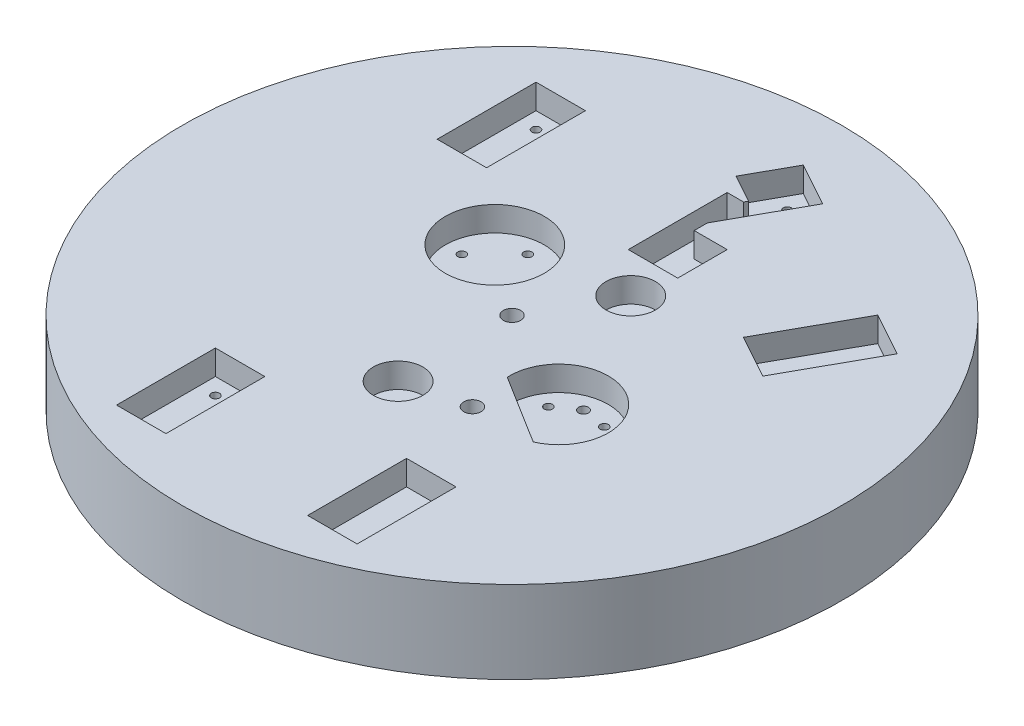
SolidWorks part; units mm, degrees
material "1.0045 (S355JR)"
ref_plane "Front Plane" through (0, 0, 0) normal (0, 0, 1) x (1, 0, 0)
ref_plane "Top Plane" through (0, 0, 0) normal (0, 1, 0) x (1, 0, 0)
ref_plane "Right Plane" through (0, 0, 0) normal (1, 0, 0) x (0, 0, -1)
sketch "Sketch1" plane through (0, 0, 0) normal (0, 1, 0) x (1, 0, 0)
  circle A0 centre (0, 0) radius 200
  dimension "D1" = 400
extrude "Boss-Extrude1" add sketch "Sketch1" along normal blind 50
sketch "Sketch2" plane through (0, 50, 0) normal (0, 1, 0) x (1, 0, 0)
  line L0 (-42.3277, 31.8965) -> (60.9712, -32.5462) construction
  line L1 (31.0011, -33.8863) -> (72.9452, -60.0529)
  circle A1 centre (0, -69.1139) radius 15
  arc A2 (72.9452, -60.0529) -> (31.0011, -33.8863) centre (60.9712, -32.5462) ccw
  circle A3 centre (25.6946, 46.3547) radius 15
  circle A4 centre (-42.3277, 31.8965) radius 30
  point P15 (0, 0)
  point P39 (250, 0)
  dimension "D3" = 30
  dimension "D6" = 60
  dimension "D10" = 30
  dimension "D11" = 69.1139
  dimension "D13" = 60
  dimension "D2" = 42.3277
  dimension "D4" = 31.8965
  dimension "D5" = 25.6946
  dimension "D7" = 46.3547
  dimension "D8" = 32.5462
  dimension "D9" = 60.9712
  dimension "D12" = 17
extrude "Cut-Extrude1" cut sketch "Sketch2" against normal blind 15
sketch "Sketch3" plane through (0, 50, 0) normal (0, 1, 0) x (1, 0, 0)
  line L57 (43.1123, -107.1139) -> (73.1123, -107.1139)
  line L92 (110.8144, 111.2209) -> (119.5606, 106.3728)
  line L93 (110.8144, 111.2209) -> (81.726, 58.7436)
  line L94 (81.726, 58.7436) -> (107.9646, 44.1994)
  line L95 (107.9646, 44.1994) -> (137.053, 96.6767)
  line L96 (137.053, 96.6767) -> (110.8144, 111.2209)
  line L97 (-85.3277, 129.8965) -> (-115.3277, 129.8965)
  line L98 (-115.3277, 129.8965) -> (-115.3277, 69.8965)
  line L99 (-115.3277, 69.8965) -> (-85.3277, 69.8965)
  line L100 (-85.3277, 129.8965) -> (-85.3277, 69.8965)
  line L104 (73.1123, -107.1139) -> (73.1123, -167.1139)
  line L107 (73.1123, -167.1139) -> (43.1123, -167.1139)
  line L108 (-42.8877, -107.1139) -> (-72.8877, -107.1139)
  line L109 (-72.8877, -107.1139) -> (-72.8877, -167.1139)
  line L110 (-72.8877, -167.1139) -> (-42.8877, -167.1139)
  line L111 (-42.8877, -107.1139) -> (-42.8877, -167.1139)
  line L112 (43.1123, -107.1139) -> (43.1123, -167.1139)
  line L113 (9.3583, 167.4584) -> (35.597, 152.9142)
  line L114 (0.6723, 129.8965) -> (10.6723, 129.8965)
  line L116 (0.6723, 69.8965) -> (30.6723, 69.8965)
  line L117 (30.6723, 99.8965) -> (30.6723, 69.8965)
  line L118 (35.597, 152.9142) -> (10.6723, 107.9486)
  line L120 (-5.1859, 141.2198) -> (9.3583, 167.4584)
  line L121 (30.6723, 99.8965) -> (10.6723, 99.8965)
  line L122 (10.6723, 99.8965) -> (10.6723, 107.9486)
  line L123 (10.6723, 129.8965) -> (11.7464, 131.8342)
  line L124 (-5.1859, 141.2198) -> (11.7464, 131.8342)
  line L125 (0.6723, 129.8965) -> (0.6723, 69.8965)
  line L126 (81.726, 58.7436) -> (10.6723, 98.129) construction
  line L127 (10.6723, 129.8965) -> (10.6723, 98.129) construction
  point P0 (0, 0)
  point P57 (0, 0)
  dimension "D2" = 81.726
  dimension "D3" = 10
  dimension "D4" = 58.7436
  dimension "D5" = 30
  dimension "D6" = 107.9646
  dimension "D7" = 111.2209
  dimension "D8" = 30
  dimension "D9" = 69.8965
  dimension "D10" = 60
  dimension "D11" = 30
  dimension "D12" = 30
  dimension "D13" = 30
  dimension "D14" = 30
  dimension "D16" = 86
  dimension "D17" = 20
  dimension "D18" = 30
  dimension "D19" = 60
  dimension "D15" = 30.6723
  dimension "D20" = 30
  dimension "D21" = 60
  dimension "D22" = 43.1123
  dimension "D23" = 107.1139
  dimension "D24" = 107.1139
  dimension "D25" = 42.8877
  dimension "D26" = 2.2155
  dimension "D27" = 85.3277
hole_wizard "M12x1.5 Tapped Hole1" positions "Sketch14" profile "Sketch15" tap size "M12x1.5" standard "ISO"
sketch "Sketch14" plane through (0, 35, 0) normal (0, 1, 0) x (1, 0, 0)
  point P0 (25.6946, 46.3547)
  point P3 (0, -69.1139)
sketch "Sketch15" plane through (25.6946, 35, -46.3547) normal (1, 0, 0) x (0, 0, 1)
  line L0 (0, 0) -> (0, 28.5)
  line L1 (0, 28.5) -> (5.25, 25.3455)
  line L2 (5.25, 25.3455) -> (5.25, 0)
  line L5 (5.25, 0) -> (0, 0)
  line L10 (0, 28.5) -> (-5.25, 25.3455) construction
  line L11 (0, -6.35) -> (0, 107.95) construction
  dimension "Tap Drill Dia." = 10.5
  dimension "Tap Drill Depth" = 28.5
  dimension "Drill Angle" = 118
cosmetic thread "Hole Thread41" parameters "D1"=24, "D2"=12
cosmetic thread "Hole Thread42" parameters "D1"=24, "D2"=12
sketch "Sketch16" plane through (0, 35, 0) normal (0, 1, 0) x (1, 0, 0)
  line L0 (-42.3277, 31.8965) -> (60.9712, -32.5462) construction
  circle A0 centre (44.0024, -21.9603) radius 3
  point P4 (-42.3277, 31.8965)
  point P6 (60.9712, -32.5462)
  dimension "D1" = 6
  dimension "D2" = 20
hole_wizard "M6 Tapped Hole1" positions "Sketch17" profile "Sketch18" tap size "M6" standard "ISO"
sketch "Sketch17" plane through (0, 35, 0) normal (0, 1, 0) x (1, 0, 0)
  point P0 (44.0024, -21.9603)
sketch "Sketch18" plane through (44.0024, 35, 21.9603) normal (1, 0, 0) x (0, 0, 1)
  line L0 (0, 0) -> (0, 15)
  line L1 (0, 15) -> (2.5, 13.4978)
  line L2 (2.5, 13.4978) -> (2.5, 0)
  line L5 (2.5, 0) -> (0, 0)
  line L10 (0, 15) -> (-2.5, 13.4978) construction
  line L11 (0, -6.35) -> (0, 107.95) construction
  dimension "Tap Drill Dia." = 5
  dimension "Tap Drill Depth" = 15
  dimension "Drill Angle" = 118
cosmetic thread "Hole Thread49" parameters "D1"=12, "D2"=6
pattern_circular "CirPattern5" count 3 over 180 about axis through (60.9712, 35, 32.5462) along (0, 1, 0) of "M6 Tapped Hole1" reverse direction yes
cosmetic thread "Hole Thread50" parameters "D1"=12, "D2"=6
cosmetic thread "Hole Thread51" parameters "D1"=12, "D2"=6
cosmetic thread "Hole Thread52" parameters "D1"=12, "D2"=6
cosmetic thread "Hole Thread81" parameters "D1"=12, "D2"=6
sketch "Sketch19" plane through (0, 35, 0) normal (0, 1, 0) x (1, 0, 0)
  circle A0 centre (-42.3277, 51.8965) radius 2
  point P2 (-42.3277, 31.8965)
  dimension "D1" = 4
  dimension "D2" = 20
hole_wizard "M6 Tapped Hole2" positions "Sketch20" profile "Sketch21" tap size "M6" standard "ISO"
sketch "Sketch20" plane through (0, 35, 0) normal (0, 1, 0) x (1, 0, 0)
  point P0 (-42.3277, 51.8965)
sketch "Sketch21" plane through (-42.3277, 35, -51.8965) normal (1, 0, 0) x (0, 0, 1)
  line L0 (0, 0) -> (0, 15)
  line L1 (0, 15) -> (2.5, 13.4978)
  line L2 (2.5, 13.4978) -> (2.5, 0)
  line L5 (2.5, 0) -> (0, 0)
  line L10 (0, 15) -> (-2.5, 13.4978) construction
  line L11 (0, -6.35) -> (0, 107.95) construction
  dimension "Tap Drill Dia." = 5
  dimension "Tap Drill Depth" = 15
  dimension "Drill Angle" = 118
cosmetic thread "Hole Thread53" parameters "D1"=12, "D2"=6
pattern_circular "CirPattern6" count 4 over 360 about axis through (-42.3277, 35, -31.8965) along (0, 1, 0) of "M6 Tapped Hole2"
cosmetic thread "Hole Thread54" parameters "D1"=12, "D2"=6
cosmetic thread "Hole Thread55" parameters "D1"=12, "D2"=6
cosmetic thread "Hole Thread56" parameters "D1"=12, "D2"=6
sketch "Sketch22" plane through (0, 50, 0) normal (0, 1, 0) x (1, 0, 0)
  line L2 (35.989, -60.0062) -> (-0.0148, 0.0248) construction
  circle A1 centre (-0.0148, 0.0248) radius 4
  circle A2 centre (35.989, -60.0062) radius 6
  dimension "D4" = 8
  dimension "D1" = 12
  dimension "D3" = 70
hole_wizard "M12x1.5 Tapped Hole2" positions "Sketch25" profile "Sketch26" tap size "M12x1.5" standard "ISO"
sketch "Sketch25" plane through (0, 50, 0) normal (0, 1, 0) x (1, 0, 0)
  point P0 (-0.0148, 0.0248)
sketch "Sketch26" plane through (-0.0148, 50, -0.0248) normal (1, 0, 0) x (0, 0, 1)
  line L0 (0, 0) -> (0, 28.5)
  line L1 (0, 28.5) -> (5.25, 25.3455)
  line L2 (5.25, 25.3455) -> (5.25, 0)
  line L5 (5.25, 0) -> (0, 0)
  line L10 (0, 28.5) -> (-5.25, 25.3455) construction
  line L11 (0, -6.35) -> (0, 107.95) construction
  dimension "Tap Drill Dia." = 10.5
  dimension "Tap Drill Depth" = 28.5
  dimension "Drill Angle" = 118
cosmetic thread "Hole Thread86" parameters "D1"=24, "D2"=12
extrude "Cut-Extrude2" cut sketch "Sketch3" against normal blind 15 contours L100 L97 L98 L99 | L95 L96 L92 L93 L94 | L111 L108 L109 L110 | L112 L107 L104 L57 | L117 L116 L125 L114 L123 L124 L120 L113 L118 L122 L121 region at (109.3895, 50, -77.7101) region at (-100.3277, 50, -99.8965) region at (-57.8877, 50, 137.1139)
sketch "Sketch27" plane through (0, 35, 0) normal (0, 1, 0) x (1, 0, 0)
  line L0 (137.053, 96.6767) -> (110.8144, 111.2209) construction
  line L1 (107.9646, 44.1994) -> (137.053, 96.6767) construction
  line L2 (30.6723, 99.8965) -> (30.6723, 69.8965) construction
  line L3 (81.726, 58.7436) -> (107.9646, 44.1994) construction
  line L4 (-115.3277, 129.8965) -> (-115.3277, 69.8965) construction
  line L5 (-85.3277, 129.8965) -> (-115.3277, 129.8965) construction
  line L6 (-115.3277, 69.8965) -> (-85.3277, 69.8965) construction
  line L7 (-42.8877, -107.1139) -> (-72.8877, -107.1139) construction
  line L8 (-72.8877, -107.1139) -> (-72.8877, -167.1139) construction
  line L9 (-72.8877, -167.1139) -> (-42.8877, -167.1139) construction
  line L10 (0.6723, 69.8965) -> (30.6723, 69.8965) construction
  line L11 (-72.8877, -107.1139) -> (-72.8877, -167.1139) construction
  line L12 (73.1123, -107.1139) -> (73.1123, -167.1139) construction
  line L13 (43.1123, -107.1139) -> (73.1123, -107.1139) construction
  line L14 (73.1123, -167.1139) -> (43.1123, -167.1139) construction
  line L15 (9.3583, 167.4584) -> (35.597, 152.9142) construction
  line L16 (-5.1859, 141.2198) -> (9.3583, 167.4584) construction
  circle A0 centre (123.4587, 92.7785) radius 3
  circle A1 centre (104.0665, 57.7937) radius 3
  circle A2 centre (-105.3277, 119.8965) radius 3
  circle A3 centre (-105.3277, 79.8965) radius 3
  circle A4 centre (-62.8877, -117.1139) radius 3
  circle A5 centre (-62.8877, -157.1139) radius 3
  circle A6 centre (63.1123, -117.1139) radius 3
  circle A7 centre (63.1123, -157.1139) radius 3
  circle A8 centre (20.6723, 79.8965) radius 3
  circle A9 centre (13.2565, 153.8642) radius 3
  dimension "D1" = 6
  dimension "D2" = 6
  dimension "D9" = 6
  dimension "D10" = 6
  dimension "D14" = 10
  dimension "D15" = 6
  dimension "D18" = 6
  dimension "D20" = 10
  dimension "D22" = 10
  dimension "D23" = 6
  dimension "D24" = 6
  dimension "D25" = 6
  dimension "D30" = 6
  dimension "D3" = 10
  dimension "D4" = 10
  dimension "D5" = 10
  dimension "D6" = 10
  dimension "D7" = 10
  dimension "D8" = 10
  dimension "D11" = 10
  dimension "D12" = 10
  dimension "D13" = 10
  dimension "D16" = 10
  dimension "D17" = 10
  dimension "D19" = 10
  dimension "D21" = 10
  dimension "D26" = 10
  dimension "D27" = 10
  dimension "D28" = 10
  dimension "D29" = 10
hole_wizard "M6 Tapped Hole3" positions "Sketch30" profile "Sketch31" tap size "M6" standard "ISO"
sketch "Sketch30" plane through (0, 35, 0) normal (0, 1, 0) x (1, 0, 0)
  point P0 (123.4587, 92.7785)
  point P3 (104.0665, 57.7937)
  point P6 (-105.3277, 119.8965)
  point P9 (-105.3277, 79.8965)
  point P12 (-62.8877, -117.1139)
  point P15 (-62.8877, -157.1139)
  point P18 (63.1123, -117.1139)
  point P21 (63.1123, -157.1139)
  point P24 (13.2565, 153.8642)
  point P27 (20.6723, 79.8965)
sketch "Sketch31" plane through (123.4587, 35, -92.7785) normal (1, 0, 0) x (0, 0, 1)
  line L0 (0, 0) -> (0, 15)
  line L1 (0, 15) -> (2.5, 13.4978)
  line L2 (2.5, 13.4978) -> (2.5, 0)
  line L5 (2.5, 0) -> (0, 0)
  line L10 (0, 15) -> (-2.5, 13.4978) construction
  line L11 (0, -6.35) -> (0, 107.95) construction
  dimension "Tap Drill Dia." = 5
  dimension "Tap Drill Depth" = 15
  dimension "Drill Angle" = 118
cosmetic thread "Hole Thread87" parameters "D1"=12, "D2"=6
cosmetic thread "Hole Thread88" parameters "D1"=12, "D2"=6
cosmetic thread "Hole Thread89" parameters "D1"=12, "D2"=6
cosmetic thread "Hole Thread90" parameters "D1"=12, "D2"=6
cosmetic thread "Hole Thread91" parameters "D1"=12, "D2"=6
cosmetic thread "Hole Thread92" parameters "D1"=12, "D2"=6
cosmetic thread "Hole Thread93" parameters "D1"=12, "D2"=6
cosmetic thread "Hole Thread94" parameters "D1"=12, "D2"=6
cosmetic thread "Hole Thread95" parameters "D1"=12, "D2"=6
cosmetic thread "Hole Thread96" parameters "D1"=12, "D2"=6
sketch "Sketch32" plane through (0, 35, 0) normal (0, 1, 0) x (1, 0, 0)
  line L0 (60.9712, -32.5462) -> (44.0024, -21.9603) construction
  line L1 (56.4578, -13.0621) -> (60.9712, -32.5462) construction
  circle A0 centre (56.4578, -13.0621) radius 3
  arc A1 (72.9452, -60.0529) -> (31.0011, -33.8863) centre (60.9712, -32.5462) ccw construction
  dimension "D1" = 6
  dimension "D2" = 20
  dimension "D3" = 45
extrude "Cut-Extrude3" cut sketch "Sketch32" against normal blind 15
hole_wizard "M12x1.5 Tapped Hole3" positions "Sketch33" profile "Sketch34" tap size "M12x1.5" standard "ISO"
sketch "Sketch33" plane through (0, 50, 0) normal (0, 1, 0) x (1, 0, 0)
  point P0 (35.989, -60.0062)
sketch "Sketch34" plane through (35.989, 50, 60.0062) normal (1, 0, 0) x (0, 0, 1)
  line L0 (0, 0) -> (0, 28.5)
  line L1 (0, 28.5) -> (5.25, 25.3455)
  line L2 (5.25, 25.3455) -> (5.25, 0)
  line L5 (5.25, 0) -> (0, 0)
  line L10 (0, 28.5) -> (-5.25, 25.3455) construction
  line L11 (0, -6.35) -> (0, 107.95) construction
  dimension "Tap Drill Dia." = 10.5
  dimension "Tap Drill Depth" = 28.5
  dimension "Drill Angle" = 118
cosmetic thread "Hole Thread97" parameters "D1"=24, "D2"=12
